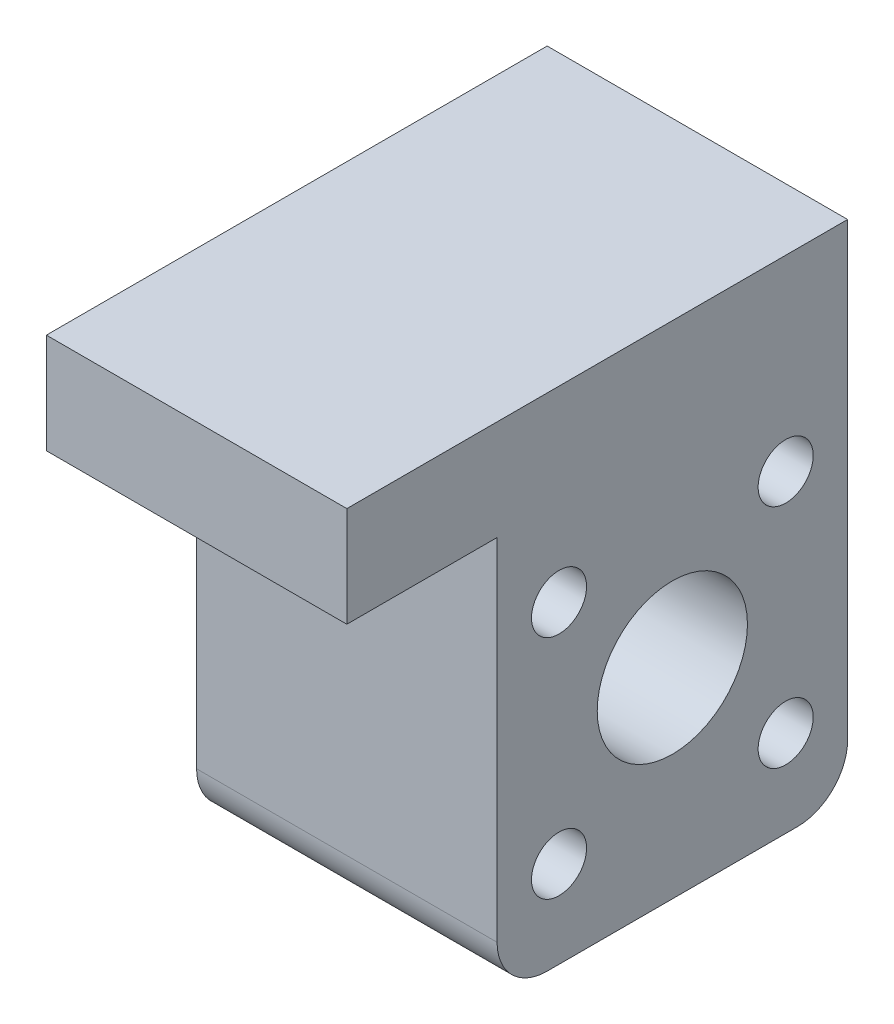
SolidWorks part; units mm, degrees
ref_plane "前视基准面" through (0, 0, 0) normal (0, 0, 1) x (1, 0, 0)
ref_plane "上视基准面" through (0, 0, 0) normal (0, 1, 0) x (1, 0, 0)
ref_plane "右视基准面" through (0, 0, 0) normal (1, 0, 0) x (0, 0, -1)
other "Configuration Table"
sketch "草图2" plane through (0, 0, 0) normal (1, 0, 0) x (0, 0, -1)
  line L1 (-17.5, -25) -> (17.5, -25)
  line L2 (-17.5, -25) -> (-17.5, 25)
  line L3 (-17.5, 25) -> (17.5, 25)
  line L4 (17.5, -25) -> (17.5, 25)
  line L5 (-17.5, -25) -> (17.5, 25) construction
  line L6 (-17.5, 25) -> (17.5, -25) construction
  point P0 (0, 0)
  dimension "D1" = 35
  dimension "D2" = 50
extrude "凸台-拉伸1" add sketch "草图2" along normal blind 30
sketch "草图3" plane through (30, 0, 0) normal (1, 0, 0) x (0, 0, -1)
  line L0 (-17.5, -25) -> (17.5, -25) construction
  line L1 (17.5, -25) -> (17.5, 25) construction
  circle A0 centre (0, -5) radius 7.5
  dimension "D1" = 15
  dimension "D2" = 20
  dimension "D3" = 17.5
extrude "切除-拉伸1" cut sketch "草图3" against normal through all and the other way through all
fillet "圆角1" radius 5 1 edges at (15, -25, -17.5)
fillet "圆角2" radius 5 1 edges at (15, -25, 17.5)
sketch "草图4" plane through (0, 0, 0) normal (-1, 0, 0) x (0, 0, 1)
  circle A1 centre (11.3137, 6.3137) radius 2.75
  circle A2 centre (11.3137, 6.3137) radius 2.75
  circle A5 centre (-11.3137, 6.3137) radius 2.75
  circle A6 centre (-11.3137, 6.3137) radius 2.75
  circle A7 centre (-11.3137, -16.3137) radius 2.75
  circle A8 centre (-11.3137, -16.3137) radius 2.75
  circle A11 centre (11.3137, -16.3137) radius 2.75
  circle A12 centre (11.3137, -16.3137) radius 2.75
  dimension "D1" = 0
  dimension "D3" = 0
  dimension "D4" = 0
  dimension "D6" = 0
extrude "切除-拉伸2" cut sketch "草图4" against normal through all
sketch "草图5" plane through (0, 25, 0) normal (0, 1, 0) x (1, 0, 0)
  line L0 (30, 17.5) -> (30, -17.5) construction
  line L1 (30, -32.5) -> (0, -32.5)
  line L2 (30, -32.5) -> (30, -17.5)
  line L3 (30, -17.5) -> (0, -17.5)
  line L4 (0, -32.5) -> (0, -17.5)
  dimension "D1" = 15
extrude "凸台-拉伸2" add sketch "草图5" against normal blind 10
